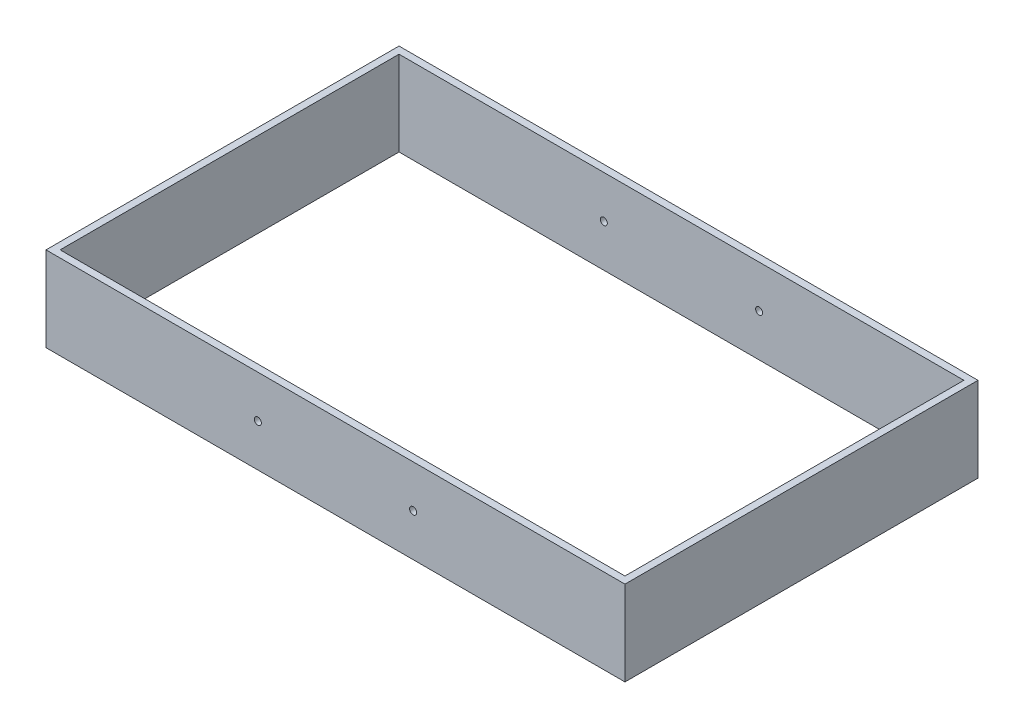
SolidWorks part; units mm, degrees
ref_plane "Front Plane" through (0, 0, 0) normal (0, 0, 1) x (1, 0, 0)
ref_plane "Top Plane" through (0, 0, 0) normal (0, 1, 0) x (1, 0, 0)
ref_plane "Right Plane" through (0, 0, 0) normal (1, 0, 0) x (0, 0, -1)
sketch "Sketch2" plane through (0, 0, 0) normal (0, 1, 0) x (1, 0, 0)
  line L1 (-72.0725, 0) -> (-72.0725, 158.75)
  line L4 (-75.2475, -3.175) -> (-75.2475, 161.925)
  line L19 (53.2587, 0) -> (53.2587, -3.175)
  line L20 (-72.0725, 158.75) -> (0, 158.75) construction
  line L21 (0, 0) -> (-72.0725, 0) construction
  line L25 (-75.2475, -3.175) -> (53.2587, -3.175)
  line L26 (0, -3.175) -> (-75.2475, -3.175) construction
  line L27 (-72.0725, 0) -> (53.2587, 0)
  line L28 (-75.2475, 161.925) -> (16.1925, 161.925)
  line L29 (-75.2475, 161.925) -> (0, 161.925) construction
  line L30 (-72.0725, 158.75) -> (16.1925, 158.75)
  line L35 (16.1925, 161.925) -> (53.2587, 161.925)
  line L36 (53.2587, 161.925) -> (53.2587, 158.75)
  line L37 (53.2587, 158.75) -> (16.1925, 158.75)
  dimension "D7" = 75.2475
  dimension "D1" = 128.5062
  dimension "D2" = 158.75
  dimension "D3" = 3.175
  dimension "D5" = 3.175
  dimension "D6" = 128.5062
  dimension "D8" = 158.75
  dimension "D4" = 3.175
ref_plane "Plane1" through (0, -38.1, 0) normal (0, 1, 0) x (1, 0, 0)
sketch "Sketch4" plane through (0, 0, 0) normal (0, 1, 0) x (1, 0, 0)
  line L14 (-3.175, -3.175) -> (-3.175, 155.575)
  line L15 (0, 0) -> (254, 0)
  line L16 (0, 0) -> (0, 152.4)
  line L17 (0, 152.4) -> (254, 152.4)
  line L18 (254, 0) -> (254, 152.4)
  line L19 (-3.175, 155.575) -> (257.175, 155.575)
  line L20 (257.175, -3.175) -> (257.175, 155.575)
  line L21 (-3.175, -3.175) -> (257.175, -3.175)
  dimension "D1" = 152.4
  dimension "D2" = 254
  dimension "D3" = 3.175
extrude "Boss-Extrude1" add sketch "Sketch4" along normal blind 38.1 contours L20 L19 L14 L21 | L17 L18 L15 L16
sketch "Sketch5" plane through (0, 0, 3.175) normal (0, 0, 1) x (1, 0, 0)
  line L0 (-3.175, 38.1) -> (-3.175, 0) construction
  line L1 (-3.175, 0) -> (257.175, 0) construction
  line L2 (-3.175, 38.1) -> (257.175, 38.1) construction
  circle A0 centre (92.075, 19.05) radius 1.5875
  circle A1 centre (161.925, 19.05) radius 1.5875
  point P0 (60.325, 19.05)
  point P1 (161.925, 19.05)
  point P2 (92.075, 19.05)
  point P3 (193.675, 19.05)
  point P4 (127, 19.05)
  dimension "D11" = 3.175
  dimension "D12" = 3.175
  dimension "D1" = 130.175
  dimension "D2" = 19.05
  dimension "D3" = 66.675
  dimension "D4" = 19.05
  dimension "D5" = 66.675
  dimension "D6" = 19.05
  dimension "D7" = 31.75
  dimension "D8" = 31.75
  dimension "D9" = 19.05
  dimension "D10" = 19.05
extrude "Cut-Extrude1" cut sketch "Sketch5" against normal through all contours A0
extrude "Cut-Extrude2" cut sketch "Sketch5<4>" against normal through all contours A1
sketch "Sketch5<4>" plane through (0, 0, 3.175) normal (0, 0, 1) x (1, 0, 0) same geometry as "Sketch5"
